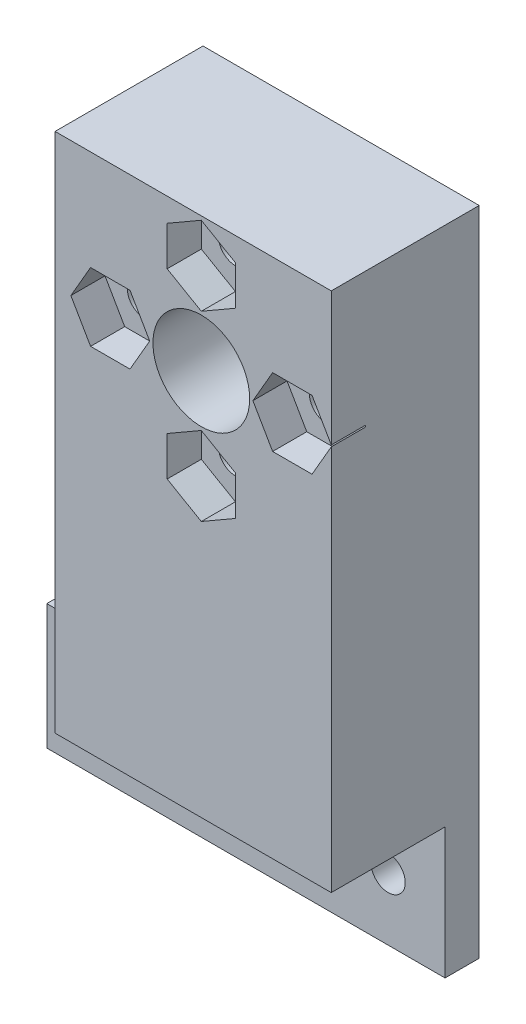
SolidWorks part; units mm, degrees
ref_plane "Front Plane" through (0, 0, 0) normal (0, 0, 1) x (1, 0, 0)
ref_plane "Top Plane" through (0, 0, 0) normal (0, 1, 0) x (1, 0, 0)
ref_plane "Right Plane" through (0, 0, 0) normal (1, 0, 0) x (0, 0, -1)
sketch "Sketch1" plane through (0, 0, 0) normal (0, 0, 1) x (1, 0, 0)
  line L0 (-449.5, -5.5) -> (-0.5, -5.5) construction
  line L1 (-57.5, -5.5) -> (-67.5, -5.5)
  line L2 (-57.5, -5.5) -> (-57.5, 5.5)
  line L3 (-57.5, 5.5) -> (-67.5, 5.5)
  line L4 (-67.5, -5.5) -> (-67.5, 5.5)
  line L5 (-0.5, 5.5) -> (-449.5, 5.5) construction
  line L6 (-449.5, 6) -> (-0.5, 6) construction
  line L7 (-60.7679, 3) -> (-64.2321, 3)
  line L8 (-64.2321, 3) -> (-65.9641, 0)
  line L9 (-65.9641, 0) -> (-64.2321, -3)
  line L10 (-64.2321, -3) -> (-60.7679, -3)
  line L11 (-60.7679, -3) -> (-59.0359, 0)
  line L12 (-59.0359, 0) -> (-60.7679, 3)
  line L13 (-64.9962, 33.1999) -> (-61.0702, 39.9999)
  line L14 (-61.0702, 39.9999) -> (-64.9962, 46.7999)
  line L15 (-64.9962, 46.7999) -> (-72.8482, 46.7999)
  line L16 (-72.8482, 46.7999) -> (-76.7742, 39.9999)
  line L17 (-76.7742, 39.9999) -> (-72.8482, 33.1999)
  line L18 (-72.8482, 33.1999) -> (-64.9962, 33.1999)
  line L19 (-81.7742, 51.7999) -> (-57.5, 51.7999)
  line L20 (-81.7742, 51.7999) -> (-81.7742, 5.5)
  line L21 (-81.7742, 5.5) -> (-57.5, 5.5)
  line L22 (-57.5, 51.7999) -> (-57.5, 5.5)
  line L23 (-81.7742, 5.5) -> (-67.5, 5.5)
  line L24 (-81.7742, 5.5) -> (-81.7742, -5.5)
  line L25 (-81.7742, -5.5) -> (-67.5, -5.5)
  line L26 (-67.5, 5.5) -> (-67.5, -5.5)
  line L27 (-81.7742, 6) -> (-57.5, 6)
  line L28 (-81.7742, 6) -> (-81.7742, 8)
  line L29 (-81.7742, 8) -> (-57.5, 8)
  line L30 (-57.5, 6) -> (-57.5, 8)
  line L32 (-81.7742, -5.5) -> (-92.5, -5.5)
  line L33 (-81.7742, -5.5) -> (-81.7742, 5.5)
  line L34 (-81.7742, 5.5) -> (-92.5, 5.5)
  line L35 (-92.5, -5.5) -> (-92.5, 5.5)
  line L36 (-81.7742, -5.5) -> (-92.5, 5.5) construction
  line L37 (-81.7742, 5.5) -> (-92.5, -5.5) construction
  line L38 (-87.5, -3.4641) -> (-84.5, -1.7321)
  line L39 (-84.5, -1.7321) -> (-84.5, 1.7321)
  line L40 (-84.5, 1.7321) -> (-87.5, 3.4641)
  line L41 (-87.5, 3.4641) -> (-90.5, 1.7321)
  line L42 (-90.5, 1.7321) -> (-90.5, -1.7321)
  line L43 (-90.5, -1.7321) -> (-87.5, -3.4641)
  circle A0 centre (-62.5, 0) radius 1.75 construction
  circle A1 centre (-62.5, 0) radius 3 construction
  circle A2 centre (-68.9222, 39.9999) radius 6.8 construction
  arc A3 (-69.0526, 43.4562) -> (-72.3763, 39.8216) centre (-68.9222, 39.9999) ccw construction
  circle A4 centre (-68.9222, 39.9999) radius 4.25
  circle A5 centre (-62.5, 0) radius 1.5
  circle A6 centre (-87.5, 0) radius 1.5
  circle A7 centre (-87.5, 0) radius 3 construction
  point P45 (-87.1371, 0)
  point P47 (-87.5, 0)
  dimension "D2" = 5
  dimension "D9" = 8.5
  dimension "D10" = 3
  dimension "D11" = 3
  dimension "D12" = 25
  dimension "D13" = 5
  dimension "D1" = 5
  dimension "D3" = 6
  dimension "D4" = 13.6
  dimension "D5" = 5
  dimension "D6" = 5
  dimension "D7" = 0
  dimension "D8" = 2
  dimension "D14" = 6
  dimension "D15" = 5.5
extrude "Boss-Extrude1" add sketch "Sketch1" along normal blind 2 contours L20 L29 L22 L19 L18 L17 L16 L15 L14 L13 | L29 L20 L27 L22 | L17 L18 L13 L14 L15 L16 region at (-69.6371, 7, 0) region at (-69.7639, 28.1084, 0) region at (-68.9222, 33.4077, 0)
extrude "Boss-Extrude2" add sketch "Sketch1<3>" against normal up to surface (8 mm away) contours L29 L20 L27 L22 | L20 L29 L22 L19 L18 L17 L16 L15 L14 L13 region at (-69.6371, 7, 0) region at (-69.7639, 28.1084, 0)
sketch "Sketch1<3>" plane through (0, 0, 0) normal (0, 0, 1) x (1, 0, 0) same geometry as "Sketch1"
extrude "Boss-Extrude3" add sketch "Sketch1<4>" against normal blind 3 from surface contours L20 L29 L22 L19 L18 L17 L16 L15 L14 L13 | L4 L1 L2 L3 L12 L11 L10 L9 L8 L7 | L27 L20 L21 L3 L22 | L29 L20 L27 L22 | L24 L25 L4 L21 | L11 L12 L7 L8 L9 L10 A5 | L35 L32 L24 L34 L43 L42 L41 L40 L39 L38 | L42 L43 L38 L39 L40 L41 A6 region at (-62.5, -5.3513, 0) region at (-74.6371, 0, 0) region at (-69.6371, 5.75, 0) region at (-87.1371, -5.3464, 0) region at (-69.6371, 7, 0) region at (-69.7639, 28.1084, 0) region at (-59.9813, 1.4542, 0) region at (-88.9542, -2.5187, 0) starting at face at (-68.9222, 39.9999, -8)
sketch "Sketch1<4>" plane through (0, 0, 0) normal (0, 0, 1) x (1, 0, 0) same geometry as "Sketch1"
extrude "Boss-Extrude4" add sketch "Sketch1<5>" against normal up to surface (11 mm away) contours L17 L18 L13 L14 L15 L16 A4 region at (-68.9222, 33.4077, 0) up to face at (-68.9222, 39.9999, -11)
sketch "Sketch1<5>" plane through (0, 0, 0) normal (0, 0, 1) x (1, 0, 0) same geometry as "Sketch1"
sketch "Sketch2" plane through (0, 0, 2) normal (0, 0, 1) x (1, 0, 0)
  line L0 (-73.4581, 39.9999) -> (-75.1901, 42.9999)
  line L1 (-68.9222, 28.5358) -> (-65.9222, 30.2679)
  line L2 (-65.9222, 30.2679) -> (-65.9222, 33.732)
  line L3 (-65.9222, 33.732) -> (-68.9222, 35.464)
  line L4 (-68.9222, 35.464) -> (-71.9222, 33.732)
  line L5 (-71.9222, 33.732) -> (-71.9222, 30.2679)
  line L6 (-71.9222, 30.2679) -> (-68.9222, 28.5358)
  line L7 (-75.1901, 36.9999) -> (-73.4581, 39.9999)
  line L8 (-78.6542, 36.9999) -> (-75.1901, 36.9999)
  line L9 (-80.3863, 39.9999) -> (-78.6542, 36.9999)
  line L10 (-78.6542, 42.9999) -> (-80.3863, 39.9999)
  line L11 (-75.1901, 42.9999) -> (-78.6542, 42.9999)
  line L12 (-68.9222, 44.5358) -> (-65.9222, 46.2679)
  line L13 (-71.9222, 46.2679) -> (-68.9222, 44.5358)
  line L14 (-71.9222, 49.732) -> (-71.9222, 46.2679)
  line L15 (-68.9222, 51.464) -> (-71.9222, 49.732)
  line L16 (-65.9222, 49.732) -> (-68.9222, 51.464)
  line L17 (-65.9222, 46.2679) -> (-65.9222, 49.732)
  line L18 (-64.3863, 39.9999) -> (-62.6542, 36.9999)
  line L19 (-62.6542, 42.9999) -> (-64.3863, 39.9999)
  line L20 (-59.1901, 42.9999) -> (-62.6542, 42.9999)
  line L21 (-57.4581, 39.9999) -> (-59.1901, 42.9999)
  line L22 (-59.1901, 36.9999) -> (-57.4581, 39.9999)
  line L23 (-62.6542, 36.9999) -> (-59.1901, 36.9999)
  circle A0 centre (-68.9222, 39.9999) radius 4.25
  circle A1 centre (-68.9222, 31.9999) radius 1.5
  circle A2 centre (-68.9222, 31.9999) radius 3 construction
  circle A3 centre (-76.9222, 39.9999) radius 1.5
  circle A4 centre (-76.9222, 39.9999) radius 3 construction
  circle A5 centre (-68.9222, 47.9999) radius 1.5
  circle A6 centre (-68.9222, 47.9999) radius 3 construction
  circle A7 centre (-60.9222, 39.9999) radius 1.5
  circle A8 centre (-60.9222, 39.9999) radius 3 construction
  point P42 (-68.9222, 39.9999)
  dimension "D1" = 3
  dimension "D5" = 8.5
  dimension "D2" = 6
  dimension "D3" = 8
  dimension "D4" = 4
extrude "Cut-Extrude1" cut sketch "Sketch2" against normal blind 3
extrude "Cut-Extrude2" cut sketch "Sketch2<2>" against normal through all contours A7 | A5 | A3 | A1 region at (-68.9222, 31.9999, 2) region at (-76.9222, 39.9999, 2) region at (-68.9222, 47.9999, 2) region at (-60.9222, 39.9999, 2)
sketch "Sketch2<2>" plane through (0, 0, 2) normal (0, 0, 1) x (1, 0, 0) same geometry as "Sketch2"
